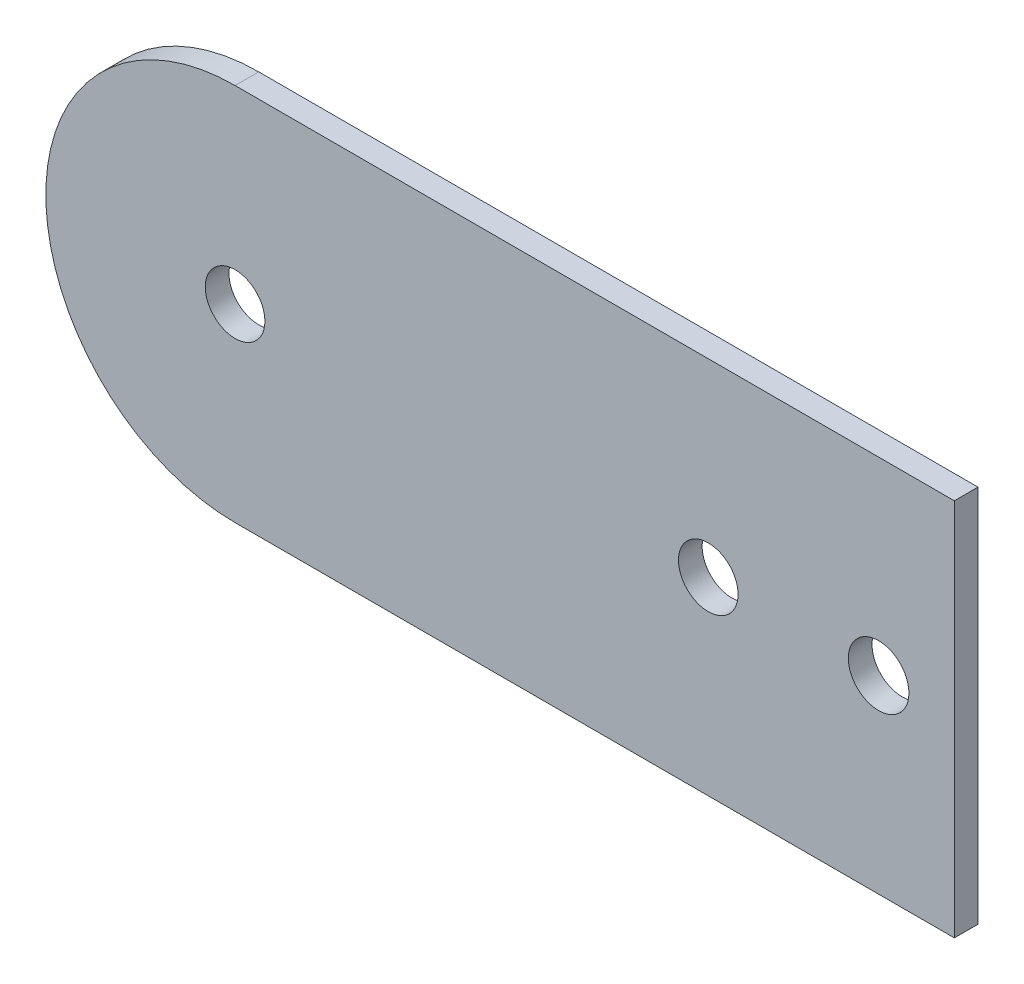
SolidWorks part; units mm, degrees
ref_plane "Front Plane" through (0, 0, 0) normal (0, 0, 1) x (1, 0, 0)
ref_plane "Top Plane" through (0, 0, 0) normal (0, 1, 0) x (1, 0, 0)
ref_plane "Right Plane" through (0, 0, 0) normal (1, 0, 0) x (0, 0, -1)
sketch "Sketch1" plane through (0, 0, 0) normal (0, 0, 1) x (1, 0, 0)
  line L0 (0, 0) -> (31.75, 0) construction
  line L1 (0, -12.7) -> (48.26, -12.7)
  line L2 (0, -12.7) -> (0, 12.7) construction
  line L3 (0, 12.7) -> (48.26, 12.7)
  line L4 (48.26, -12.7) -> (48.26, 12.7)
  line L5 (31.75, 0) -> (43.18, 0) construction
  arc A0 (0, 12.7) -> (0, -12.7) centre (0, 0) ccw
  circle A1 centre (0, 0) radius 2
  circle A2 centre (31.75, 0) radius 2
  circle A3 centre (43.18, 0) radius 2.032
  dimension "D3" = 4
  dimension "D4" = 4
  dimension "D6" = 4.064
  dimension "D1" = 25.4
  dimension "D2" = 48.26
  dimension "D5" = 31.75
  dimension "D7" = 11.43
extrude "Boss-Extrude1" add sketch "Sketch1" along normal blind 1.5875
